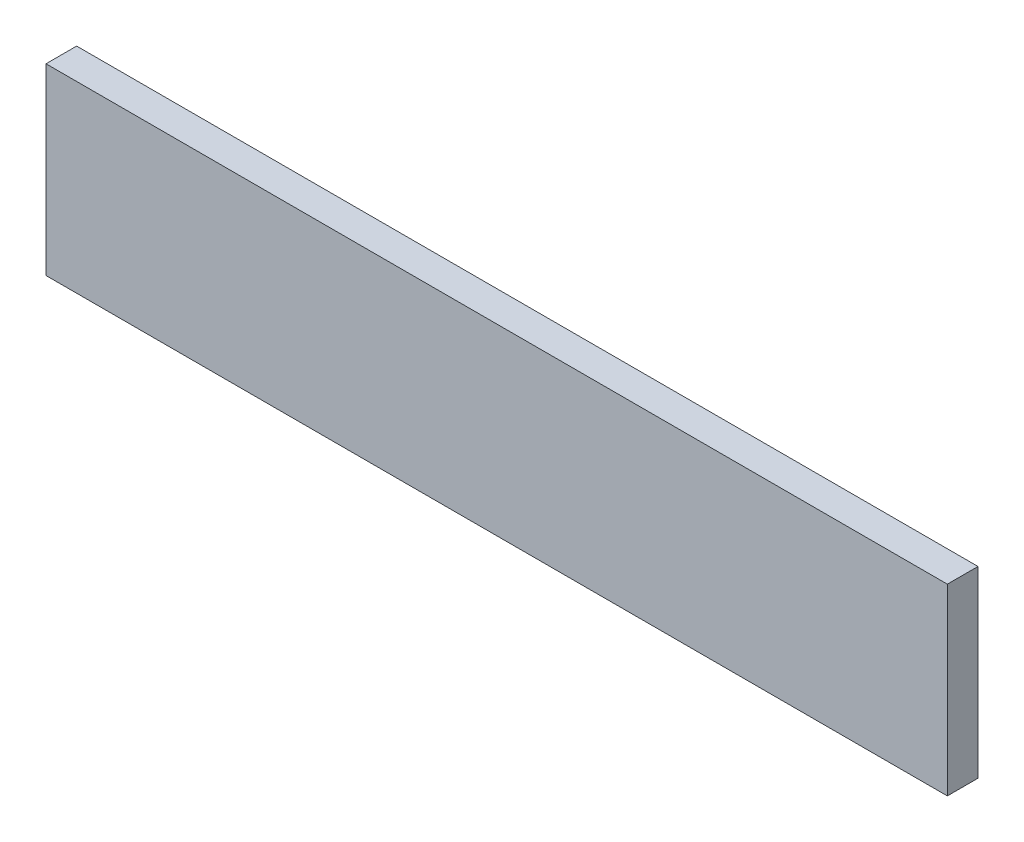
SolidWorks part; units mm, degrees
material "Plain Carbon Steel"
ref_plane "Front Plane" through (0, 0, 0) normal (0, 0, 1) x (1, 0, 0)
ref_plane "Top Plane" through (0, 0, 0) normal (0, 1, 0) x (1, 0, 0)
ref_plane "Right Plane" through (0, 0, 0) normal (1, 0, 0) x (0, 0, -1)
sketch "Sketch1" plane through (0, 0, 0) normal (0, 0, 1) x (1, 0, 0)
  line L0 (-47, -7) -> (-47, 52.8258) construction
  line L1 (-47, 52.8258) -> (247, 52.8258)
  line L2 (-47, 52.8258) -> (-47, -7)
  line L3 (-47, -7) -> (247, -7)
  line L4 (247, 52.8258) -> (247, -7)
  line L5 (-47, 52.8258) -> (247, 52.8258) construction
  line L6 (247, 52.8258) -> (247, -7) construction
  line L7 (247, -7) -> (-47, -7) construction
extrude "Boss-Extrude1" add sketch "Sketch1" along normal blind 10
